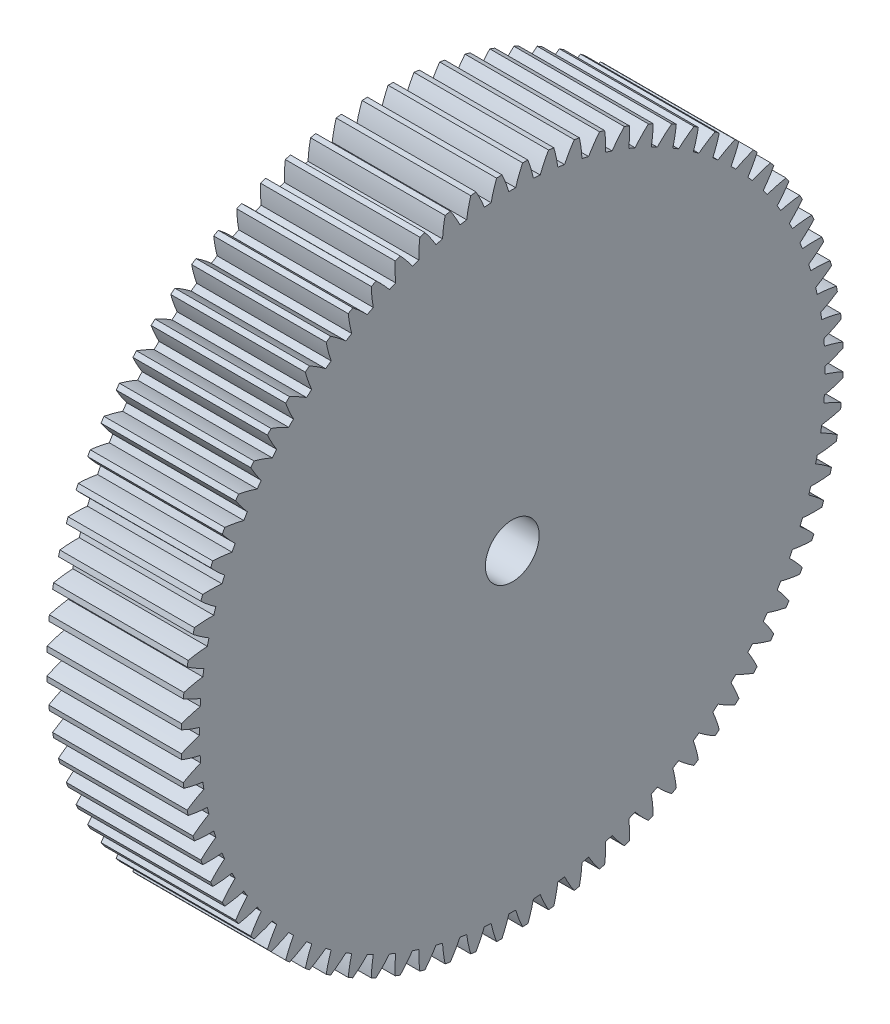
SolidWorks part; units mm, degrees
ref_plane "Plane1" through (0, 0, 0) normal (0, 0, 1) x (1, 0, 0)
ref_plane "Plane2" through (0, 0, 0) normal (0, 1, 0) x (1, 0, 0)
ref_plane "Plane3" through (0, 0, 0) normal (1, 0, 0) x (0, 0, -1)
other "Configuration Table"
sketch "HoldingSke" plane through (0, 0, 0) normal (0, 1, 0) x (1, 0, 0)
  line L0 (0, 0) -> (0.2894, -1.6413)
  line L1 (-15, 0) -> (100, 0) construction
  line L2 (0, 0) -> (-2.1039, 2.3779)
  line L3 (0, 0) -> (-11.863, 4.5341)
  line L4 (0, 0) -> (1.4996, 8.5048)
  line L5 (0, 0) -> (-46.8476, -17.4728)
  line L6 (0, 0) -> (-8.2896, -5.593)
  line L7 (-2.1039, 2.3779) -> (8.6586, 51.2059)
  line L8 (-76.2, 54.61) -> (-75.5, 54.61)
  line L9 (-71.009, 38.7566) -> (-53.1078, 45.2721)
  line L10 (-76.2, 71.12) -> (104.1128, 71.12)
  line L11 (0, 0) -> (-10, 0)
  line L12 (-76.2, 101.6) -> (-76.177, 101.6)
  line L13 (24.9733, 27.94) -> (52.9518, 28.4284)
  line L14 (24.9733, 27.94) -> (24.9743, 27.94)
  line L15 (24.9733, 27.94) -> (100.4006, 29.5858)
  line L16 (-63.627, -0.6) -> (-12.827, -0.6)
  circle A0 centre (0, 0) radius 2
  circle A1 centre (0, 0) radius 23.249
  circle A2 centre (0, 0) radius 37.5
  circle A3 centre (0, 0) radius 2
  dimension "Num_teeth" = 80
  dimension "Pitch_radius" = 180.3128
  dimension "Width" = 10
  dimension "Thickness" = 10
sketch "BasProSke" plane through (0, 0, 0) normal (0, 1, 0) x (1, 0, 0)
  line L0 (-10, 0) -> (60, 0) construction
  line L1 (0, 0) -> (0, 24.6)
  line L2 (0, 0) -> (10, 0)
  line L3 (10, 0) -> (10, 24.6)
  line L4 (10, 24.6) -> (0, 24.6)
  dimension "Thickness" = 10
  dimension "Diameter" = 49.2
revolve "Base-Revolve" add sketch "BasProSke" angle 360 about L0
sketch "TooCutSke" plane through (0, 0, 0) normal (1, 0, 0) x (0, 0, -1)
  line L1 (0, 0) -> (0, 107) construction
  line L2 (0, 0) -> (-0.5115, 23.9945) construction
  line L3 (0, 0) -> (-1.8842, 47.9553) construction
  line L4 (-0.5115, 23.9945) -> (-0.9421, 23.9776) construction
  arc A0 (0.2526, 23.2476) -> (-0.2526, 23.2476) centre (0, 0) ccw
  arc A1 (0.7803, 24.613) -> (-0.7803, 24.613) centre (0, 0) ccw
  circle A2 centre (0, 0) radius 24 construction
  circle A3 centre (0, 0) radius 22.5526 construction
  arc A4 (-0.2526, 23.2476) -> (-0.7803, 24.613) centre (-9.4448, 20.4796) ccw
  arc A5 (0.7803, 24.613) -> (0.2526, 23.2476) centre (9.4448, 20.4796) ccw
extrude "ToothCut" cut sketch "TooCutSke" along normal through all
fillet "Breaks" [suppressed] radius 0.012 tangent propagation no
fillet "RootFillets" [suppressed] radius 0.151
pattern_circular "TeethCuts" count 80 every 4.5 about axis through (-10, 0, 0) along (1, 0, 0) of "ToothCut", "RootFillets", "Breaks"
sketch "HubNeaOneSke" plane through (0, 0, 0) normal (-1, 0, 0) x (0, 0, 1)
  circle A0 centre (0, 0) radius 23.249
  dimension "Diameter" = 46.498
extrude "HubNearOne" [suppressed] add sketch "HubNeaOneSke" along normal blind 40.0001
sketch "HubNeaBotSke" plane through (0, 0, 0) normal (-1, 0, 0) x (0, 0, 1)
  circle A0 centre (0, 0) radius 23.249
  dimension "Diameter" = 46.498
extrude "HubNearBoth" [suppressed] add sketch "HubNeaBotSke" along normal blind 20
ref_plane "FarPln" through (10, 0, 0) normal (1, 0, 0) x (0, 0, -1)
sketch "HubFarSke" plane through (10, 0, 0) normal (1, 0, 0) x (0, 0, -1)
  circle A0 centre (0, 0) radius 23.249
  dimension "Diameter" = 46.498
extrude "HubFar" [suppressed] add sketch "HubFarSke" along normal blind 20
sketch "BorSke" plane through (0, 0, 0) normal (1, 0, 0) x (0, 0, -1)
  circle A0 centre (0, 0) radius 2
  dimension "Diameter" = 4
extrude "Bore" cut sketch "BorSke" along normal mid plane 100.0001
sketch "KeySke" plane through (0, 0, 0) normal (1, 0, 0) x (0, 0, -1)
  line L0 (-0.8, 0) -> (-0.8, 2.7)
  line L1 (-0.8, 2.7) -> (0.8, 2.7)
  line L2 (0.8, 2.7) -> (0.8, 0)
  line L3 (0, 0) -> (0, 34) construction
  line L4 (-0.8, 0) -> (0.8, 0)
  dimension "Width" = 1.6
extrude "Keyway" [suppressed] cut sketch "KeySke" along normal mid plane 100.0001
pattern_circular "Keyway2" [suppressed] count 2 every 90 about axis through (-10, 0, 0) along (1, 0, 0) reverse direction yes
equation "' \"Module@HoldingSke\" = 6.35"
equation "' \"Num_teeth@HoldingSke\" = 12"
equation "' \"Ap@HoldingSke\" =  20"
equation "' \"Ap@HoldingSke\" = 20"
equation "' \"Width@HoldingSke\" = 0.5 * 25.4"
equation "' \"Hub_dia@HoldingSke\"= 1 * 25.4"
equation "' \"Hub_dia@HoldingSke\" = 1 * 25.4"
equation "' \"Overall_len@HoldingSke\" = 1.0 * 25.4"
equation "' \"Bore@HoldingSke\" = 0.75 * 25.4"
equation "' \"T_dim@HoldingSke\" = 0.1 * 25.4"
equation "' \"Width@KeySke\" = 0.25 * 25.4"
equation "' \"Show_teeth@HoldingSke\" = 13"
equation "' \"Backlash@HoldingSke\" = 0.009 * 25.4"
equation "' \"Addendum_fac@HoldingSke\" = 1.0"
equation "' \"Dedendum_fac@HoldingSke\" = 1.25"
equation "' \"Dedendum_add@HoldingSke\" = 0.00005 * 25.4"
equation "' \"Clearance_fac@HoldingSke\" = 0.25"
equation "\"Pitch@HoldingSke\" = 1 / \"Module@HoldingSke\""
equation "\"Overcut_dia@TooCutSke\" = (\"Num_teeth@HoldingSke\" + 2 * \"Addendum_fac@HoldingSke\") / \"Pitch@HoldingSke\" + 0.002 * 25.4"
equation "\"Pitch_dia@TooCutSke\" = \"Num_teeth@HoldingSke\" / \"Pitch@HoldingSke\""
equation "\"Base_dia@TooCutSke\" = \"Num_teeth@HoldingSke\" / \"Pitch@HoldingSke\" * cos((\"Ap@HoldingSke\"  * 3.14159265 / 180))"
equation "\"Root_dia@TooCutSke\" = (\"Num_teeth@HoldingSke\" + 2) / \"Pitch@HoldingSke\" - 2 * (\"Addendum_fac@HoldingSke\" + \"Dedendum_fac@HoldingSke\") / \"Pitch@HoldingSke\" - \"Dedendum_add@HoldingSke\" * 2"
equation "\"Half_ang@TooCutSke\" = 180 / \"Num_teeth@HoldingSke\""
equation "\"Half_CT@TooCutSke\" = \"Num_teeth@HoldingSke\" / \"Pitch@HoldingSke\" * sin((3.14159265 / 2 / \"Num_teeth@HoldingSke\")) / 2 - 7 * \"Backlash@HoldingSke\" / 4"
equation "\"Flank_rad@TooCutSke\" = \"Num_teeth@HoldingSke\" / \"Pitch@HoldingSke\" / 5"
equation "\"Radius@RootFillets\" = \"Clearance_fac@HoldingSke\" / \"Pitch@HoldingSke\" + \"Dedendum_add@HoldingSke\""
equation "\"Break_rad@Breaks\" = 0.02 / \"Pitch@HoldingSke\""
equation "\"Thickness@HoldingSke\" = \"Width@HoldingSke\""
equation "\"OAL@HoldingSke\" = \"Thickness@HoldingSke\""
equation "\"MHD@HoldingSke\" = (\"Num_teeth@HoldingSke\" + 2) / \"Pitch@HoldingSke\" - 2 * (\"Addendum_fac@HoldingSke\" + \"Dedendum_fac@HoldingSke\")  / \"Pitch@HoldingSke\" - \"Dedendum_add@HoldingSke\" * 2"
equation "\"MBD@HoldingSke\" = (\"Num_teeth@HoldingSke\" + 2) / \"Pitch@HoldingSke\" - 2 * (\"Addendum_fac@HoldingSke\" + \"Dedendum_fac@HoldingSke\")  / \"Pitch@HoldingSke\" - \"Dedendum_add@HoldingSke\" * 2 - 0.002 * 25.4"
equation "\"MHD@HoldingSke\" = ((sgn( \"MHD@HoldingSke\" - \"Hub_dia@HoldingSke\" )-1)*( \"MHD@HoldingSke\" - \"Hub_dia@HoldingSke\" ))/-2+ \"Hub_dia@HoldingSke\""
equation "\"MBD@HoldingSke\" = ((sgn( \"MBD@HoldingSke\" - \"Bore@HoldingSke\" )-1)*( \"MBD@HoldingSke\" - \"Bore@HoldingSke\" ))/-2+ \"Bore@HoldingSke\""
equation "\"OAL@HoldingSke\" = ((sgn( \"OAL@HoldingSke\" - \"Overall_len@HoldingSke\" )+1)*( \"OAL@HoldingSke\" - \"Overall_len@HoldingSke\" ))/2 + \"Overall_len@HoldingSke\" + 0.000002 * 25.4"
equation "\"Num_teeth@TeethCuts\" = int( \"Show_teeth@HoldingSke\" ) + 1"
equation "\"Num_teeth@TeethCuts\" = ((sgn( \"Num_teeth@TeethCuts\" - \"Num_teeth@HoldingSke\" )-1)*( \"Num_teeth@TeethCuts\" - \"Num_teeth@HoldingSke\" ))/-2+ \"Num_teeth@HoldingSke\""
equation "\"Num_teeth@TeethCuts\" = ((sgn( \"Num_teeth@TeethCuts\" - 2.0)+1)*( \"Num_teeth@TeethCuts\" - 2.0))/2 +2.0"
equation "\"Angle@TeethCuts\" = 360.0 / \"Num_teeth@HoldingSke\""
equation "\"Diameter@BasProSke\" = (\"Num_teeth@HoldingSke\" + 2 * \"Addendum_fac@HoldingSke\") / \"Pitch@HoldingSke\""
equation "\"Thickness@BasProSke\"  = \"Thickness@HoldingSke\""
equation "' \"Fillet_rad@BasProSke\" =  \"Thickness@HoldingSke\" * 0.05"
equation "' \"Fillet_rad@BasProSke\" = \"Thickness@HoldingSke\" * 0.05"
equation "\"MHD@HoldingSke\" = ((sgn( \"MHD@HoldingSke\" - \"Root_dia@TooCutSke\" )-1)*( \"MHD@HoldingSke\" - \"Root_dia@TooCutSke\" ))/-2+ \"Root_dia@TooCutSke\""
equation "\"Diameter@HubNeaOneSke\" = \"MHD@HoldingSke\""
equation "\"Length@HubNearOne\" = \"OAL@HoldingSke\" - \"Thickness@BasProSke\""
equation "\"Diameter@HubNeaBotSke\" = \"MHD@HoldingSke\""
equation "\"Length@HubNearBoth\" = ( \"OAL@HoldingSke\" - \"Thickness@BasProSke\" ) / 2.0"
equation "\"Thickness@FarPln\" = \"Thickness@BasProSke\""
equation "\"Diameter@HubFarSke\" = \"MHD@HoldingSke\""
equation "\"Length@HubFar\" = ( \"OAL@HoldingSke\" - \"Thickness@BasProSke\" ) / 2.0"
equation "\"Diameter@BorSke\" = \"MBD@HoldingSke\""
equation "\"D1@Bore\" = \"OAL@HoldingSke\" * 2.0"
equation "\"D1@Keyway\" = \"OAL@HoldingSke\" * 2.0"
equation "\"Offset@KeySke\" = \"T_dim@HoldingSke\" + \"MBD@HoldingSke\" / 2.0"
